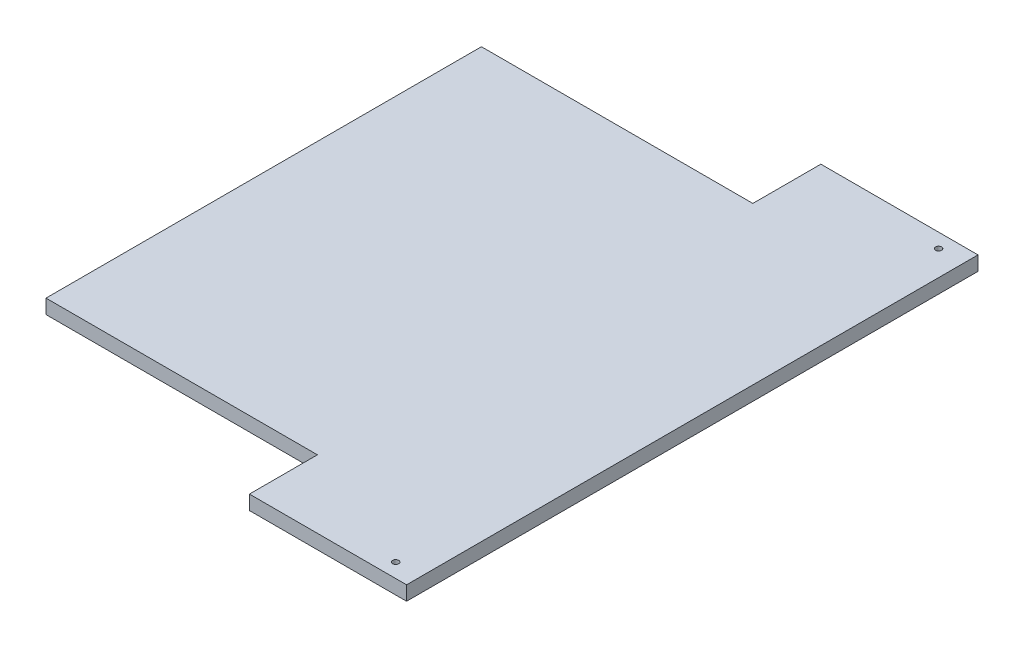
SolidWorks part; units mm, degrees
ref_plane "Front Plane" through (0, 0, 0) normal (0, 0, 1) x (1, 0, 0)
ref_plane "Top Plane" through (0, 0, 0) normal (0, 1, 0) x (1, 0, 0)
ref_plane "Right Plane" through (0, 0, 0) normal (1, 0, 0) x (0, 0, -1)
sketch "Sketch1" plane through (0, 0, 0) normal (0, 1, 0) x (1, 0, 0)
  line L0 (-190.5, 254) -> (190.5, -254) construction
  line L1 (-190.5, 254) -> (190.5, 254)
  line L2 (-190.5, 254) -> (-190.5, -254)
  line L3 (-190.5, -254) -> (190.5, -254)
  line L4 (190.5, 254) -> (190.5, -254)
  dimension "D1" = 508
  dimension "D2" = 381
extrude "Boss-Extrude1" add sketch "Sketch1" along normal mid plane 12.7
sketch "Sketch2" plane through (0, 6.35, 0) normal (0, 1, 0) x (1, 0, 0)
  line L0 (190.5, -254) -> (190.5, 254) construction
  line L5 (-190.5, -254) -> (190.5, -254) construction
  line L6 (-190.5, -254) -> (50.8, -254)
  line L7 (-190.5, -254) -> (-190.5, -193.548)
  line L8 (-190.5, -193.548) -> (50.8, -193.548)
  line L9 (50.8, -254) -> (50.8, -193.548)
  line L10 (190.5, 254) -> (-190.5, 254) construction
  line L11 (-190.5, 254) -> (50.8, 254)
  line L12 (-190.5, 254) -> (-190.5, 193.548)
  line L13 (-190.5, 193.548) -> (50.8, 193.548)
  line L14 (50.8, 254) -> (50.8, 193.548)
  dimension "D1" = 139.7
  dimension "D2" = 241.3
  dimension "D3" = 241.3
  dimension "D4" = 139.7
  dimension "D7" = 60.452
  dimension "D8" = 60.452
extrude "Cut-Extrude1" cut sketch "Sketch2" against normal blind 230.886
sketch "Sketch3" plane through (0, 6.35, 0) normal (0, 1, 0) x (1, 0, 0)
  line L0 (50.8, -254) -> (190.5, -254) construction
  line L1 (190.5, 254) -> (50.8, 254) construction
  line L2 (190.5, -254) -> (190.5, 254) construction
  line L3 (190.5, -254) -> (190.5, 254) construction
  circle A0 centre (168.148, -241.3) radius 2.667
  circle A20 centre (168.148, 241.3) radius 2.667
  dimension "D1" = 12.7
  dimension "D2" = 12.7
  dimension "D3" = 5.334
  dimension "D4" = 22.352
  dimension "D5" = 22.352
extrude "Cut-Extrude2" cut sketch "Sketch3" against normal blind 230.886
